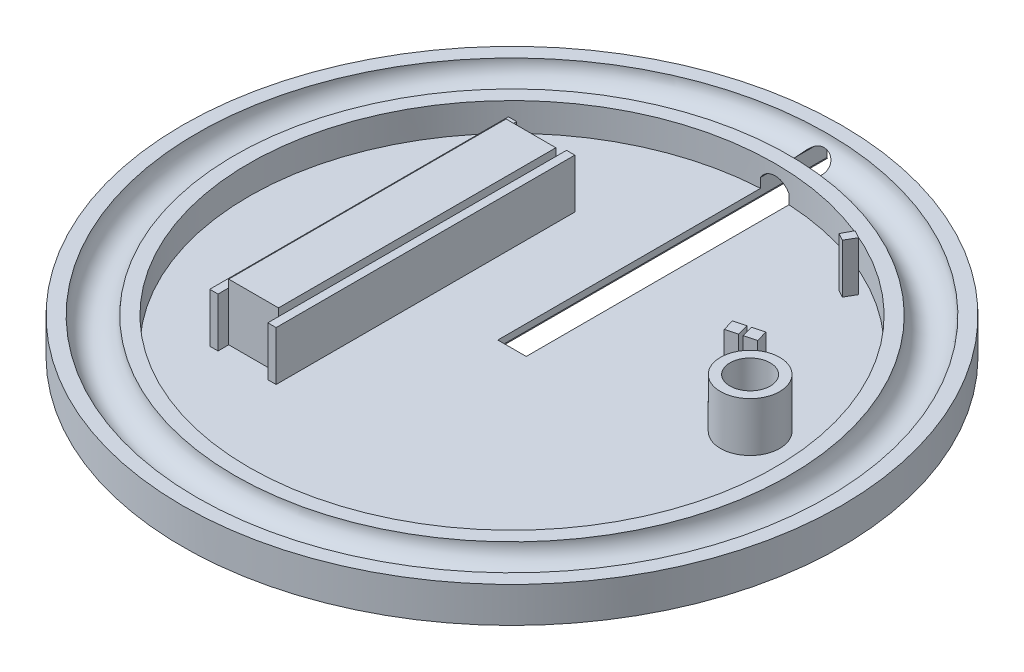
SolidWorks part; units mm, degrees
ref_plane "Front Plane" through (0, 0, 0) normal (0, 0, 1) x (1, 0, 0)
ref_plane "Top Plane" through (0, 0, 0) normal (0, 1, 0) x (1, 0, 0)
ref_plane "Right Plane" through (0, 0, 0) normal (1, 0, 0) x (0, 0, -1)
sketch "Sketch1" plane through (0, 0, 0) normal (0, 0, 1) x (1, 0, 0)
  line L0 (55, 0) -> (-55, 0) construction
  line L1 (0, 15) -> (0, 0)
  line L2 (0, 15) -> (139, 15)
  line L4 (139, 0) -> (0, 0)
  line L5 (139, 15) -> (139, 0)
  line L9 (0, 4.511) -> (0, 20.439) construction
  dimension "D1" = 139
  dimension "D4" = 15
revolve "Revolve1" add sketch "Sketch1" angle 360 about L9
sketch "Sketch2" plane through (0, 0, 0) normal (0, 0, 1) x (1, 0, 0)
  line L5 (139, 15) -> (-139, 15) construction
  line L7 (0, -8.25) -> (0, 8.25) construction
  line L8 (125, -0.0482) -> (125, 11.8) construction
  line L9 (117, 15) -> (133, 15)
  arc A0 (133, 15) -> (117, 15) centre (125, 15) cw
  point P0 (125, 15)
  dimension "D1" = 125
  dimension "D2" = 8
sketch "Sketch4" plane through (0, 15, 0) normal (0, 1, 0) x (1, 0, 0)
  line L0 (-55, 0) -> (55, 0) construction
  line L1 (-40, -58.5) -> (-61, -58.5)
  line L2 (-40, -58.5) -> (-40, 58.5)
  line L3 (-40, 58.5) -> (-61, 58.5)
  line L4 (-61, -58.5) -> (-61, 58.5)
  line L5 (-40, -58.5) -> (-61, 58.5) construction
  line L6 (-40, 58.5) -> (-61, -58.5) construction
  line L7 (0, -55) -> (0, 55) construction
  point P0 (-50.5, 0)
  dimension "D1" = 117
  dimension "D2" = 21
  dimension "D3" = 40
extrude "Boss-Extrude1" add sketch "Sketch4" along normal blind 12
sketch "Sketch5" plane through (0, 15, 0) normal (0, 1, 0) x (1, 0, 0)
  line L3 (0, 0) -> (80.5909, 19.852) construction
  line L5 (0, 0) -> (89.4848, 37.0658) construction
  line L6 (-8.25, 0) -> (8.25, 0) construction
  circle A0 centre (80.5909, 19.852) radius 12.5
  circle A1 centre (80.5909, 19.852) radius 8.5
  point P7 (0, 0)
  dimension "D1" = 25
  dimension "D2" = 22.5
  dimension "D3" = 83
  dimension "D4" = 4
extrude "Boss-Extrude2" add sketch "Sketch5" along normal blind 8.8
sketch "Sketch9" plane through (0, 15, 0) normal (0, 1, 0) x (1, 0, 0)
  line L0 (0, 0) -> (50.7046, 95.3614) construction
  line L2 (47.8861, 90.0607) -> (50.2335, 94.4754)
  line L3 (51, 88.3346) -> (53.5, 92.6647)
  line L4 (-14.85, 0) -> (14.85, 0) construction
  line L6 (0, 0) -> (54.0168, 93.5598) construction
  arc A0 (51, 88.3346) -> (47.8861, 90.0607) centre (0, 0) ccw
  arc A1 (53.5, 92.6647) -> (50.2335, 94.4754) centre (0, 0) ccw
  point P0 (0, 0)
  dimension "D2" = 102
  dimension "D3" = 107
  dimension "D1" = 60
  dimension "D5" = 2
extrude "Boss-Extrude3" add sketch "Sketch9" along normal blind 8.8
sketch "Sketch10" plane through (0, 15, 0) normal (0, 1, 0) x (1, 0, 0)
  line L0 (0, 0) -> (83.8108, 34.7156) construction
  line L1 (36.9552, 15.3073) -> (41.5746, 17.2208)
  line L2 (36.9552, 15.3073) -> (35.4244, 19.0029)
  line L3 (41.5746, 17.2208) -> (40.0438, 20.9163)
  line L4 (35.4244, 19.0029) -> (40.0438, 20.9163)
  point P0 (0, 0)
  dimension "D1" = 40
  dimension "D2" = 5
  dimension "D3" = 4
sketch "Sketch11" plane through (0, 15, 0) normal (0, 1, 0) x (1, 0, 0)
  line L0 (-50.5, 58.5) -> (-50.5, -58.5) construction
  line L1 (-40, 58.5) -> (-61, 58.5) construction
  line L2 (-61, -58.5) -> (-40, -58.5) construction
  line L3 (-14.85, 0) -> (14.85, 0) construction
  line L4 (-64.5, -63) -> (-36.5, -63)
  line L5 (-64.5, -63) -> (-64.5, 63)
  line L6 (-64.5, 63) -> (-36.5, 63)
  line L7 (-36.5, -63) -> (-36.5, 63)
  line L8 (-64.5, -63) -> (-36.5, 63) construction
  line L9 (-64.5, 63) -> (-36.5, -63) construction
  line L10 (-61, 58.5) -> (-61, -58.5)
  line L11 (-61, 58.5) -> (-61, -58.5) construction
  line L12 (-61, -58.5) -> (-40, -58.5)
  line L13 (-40, -58.5) -> (-40, 58.5)
  line L14 (-40, 58.5) -> (-61, 58.5)
  point P6 (-50.5, 0)
  dimension "D1" = 28
  dimension "D2" = 126
  dimension "D3" = 63
extrude "Boss-Extrude5" add sketch "Sketch11" along normal blind 8.8
sketch "Sketch12" plane through (0, 15, 0) normal (0, 1, 0) x (1, 0, 0)
  line L0 (80.5909, 19.852) -> (64.205, 32.3528)
  line L1 (80.5909, 19.852) -> (80.5909, 49.5381)
  line L2 (64.205, 32.3528) -> (81.5264, -30.8639) construction
  line L3 (64.205, 32.3528) -> (90.1144, 39.452) construction
  line L4 (64.9283, 32.551) -> (63.607, 37.3733)
  line L5 (64.205, 32.3528) -> (59.4962, 49.5381) construction
  line L6 (63.607, 37.3733) -> (68.4292, 38.6946)
  line L7 (68.4292, 38.6946) -> (69.7506, 33.8723)
  line L8 (69.7506, 33.8723) -> (64.9283, 32.551)
  line L9 (63.4816, 32.1546) -> (62.1603, 36.9769)
  line L10 (58.6594, 30.8333) -> (63.4816, 32.1546)
  line L11 (57.3381, 35.6556) -> (58.6594, 30.8333)
  line L12 (62.1603, 36.9769) -> (57.3381, 35.6556)
  circle A0 centre (80.5909, 19.852) radius 12.5 construction
  dimension "D1" = 20.61
  dimension "D2" = 52.66
  dimension "D3" = 5
  dimension "D4" = 5
  dimension "D5" = 0.75
sketch "Sketch13" plane through (0, 15, 0) normal (0, 1, 0) x (1, 0, 0)
  line L0 (-64.5, 63) -> (-64.5, -63) construction
  line L1 (-36.5, -63) -> (-36.5, 63) construction
  line L2 (-36.5, 63) -> (-64.5, 63) construction
  line L3 (-36.5, 63) -> (-64.5, 63)
  line L4 (-36.5, -63) -> (-36.5, 63)
  line L5 (-64.5, 63) -> (-64.5, -63)
  line L6 (-64.5, -63) -> (-36.5, -63) construction
  line L7 (-64.5, -63) -> (-36.5, -63)
  line L8 (51, 88.3346) -> (53.5, 92.6647) construction
  line L9 (50.2335, 94.4754) -> (47.8861, 90.0607) construction
  line L10 (51, 88.3346) -> (53.5, 92.6647)
  line L11 (50.2335, 94.4754) -> (47.8861, 90.0607)
  circle A0 centre (0, 0) radius 111
  circle A1 centre (0, 0) radius 139 construction
  circle A2 centre (80.5909, 19.852) radius 12.5 construction
  circle A3 centre (80.5909, 19.852) radius 12.5
  arc A4 (51, 88.3346) -> (47.8861, 90.0607) centre (0, 0) ccw construction
  arc A5 (53.5, 92.6647) -> (50.2335, 94.4754) centre (0, 0) ccw construction
  arc A6 (51, 88.3346) -> (47.8861, 90.0607) centre (0, 0) ccw
  arc A7 (53.5, 92.6647) -> (50.2335, 94.4754) centre (0, 0) ccw
  circle A8 centre (80.5909, 19.852) radius 8.5
  line M5 (53.5, 92.6647) -> (51, 88.3346)
  arc M6 (51, 88.3346) -> (47.8861, 90.0607) centre (0, 0) ccw
  line M7 (47.8861, 90.0607) -> (50.2335, 94.4754)
  arc M8 (50.2335, 94.4754) -> (53.5, 92.6647) centre (0, 0) cw
  circle M18 centre (80.5909, 19.852) radius 12.5
  line M19 (-64.5, 63) -> (-36.5, 63)
  line M20 (-36.5, 63) -> (-36.5, -63)
  line M21 (-36.5, -63) -> (-64.5, -63)
  line M22 (-64.5, -63) -> (-64.5, 63)
  dimension "D1" = 28
extrude "Cut-Extrude1" cut sketch "Sketch13" against normal offset from surface (12 mm away) 3 contours A8 | A0 M8 M5 M6 M7 M22 M19 M20 M21 M18 region at (3.9711, 15, 0.3292) region at (80.5909, 15, -19.852) up to face at (0, 0, -139)
extrude "Boss-Extrude6" add sketch "Sketch12" along normal blind 8.8 and the other way up to surface (12 mm away) contours L10 L9 L12 L11 | L7 L8 L4 L6 other way up to face at (80.5909, 3, -32.352)
sketch "Sketch14" plane through (0, 23.8, 0) normal (0, 1, 0) x (1, 0, 0)
  line L0 (-64.5, -63) -> (-36.5, -63) construction
  line L1 (-61, -58.5) -> (-40, -58.5)
  line L2 (-61, -58.5) -> (-61, -63)
  line L3 (-61, -63) -> (-40, -63)
  line L4 (-40, -58.5) -> (-40, -63)
  line L5 (-61, 58.5) -> (-40, 58.5)
  line L6 (-40, 58.5) -> (-40, 63)
  line L7 (-36.5, 63) -> (-64.5, 63) construction
  line L8 (-61, 58.5) -> (-61, 63)
  line L9 (-61, 63) -> (-40, 63)
extrude "Cut-Extrude2" cut sketch "Sketch14" against normal up to surface (20.8 mm away) up to face at (0, 3, -111)
sketch "Sketch15" plane through (0, 0, 0) normal (0, 0, 1) x (1, 0, 0)
  line L0 (139.7, 0) -> (-139.7, 0) construction
  line L1 (-6, 0) -> (6, 0)
  line L2 (-6, 0) -> (-6, 7)
  line L4 (6, 0) -> (6, 7)
  line L5 (0, -14.85) -> (0, 14.85) construction
  arc A0 (-6, 0.2572) -> (-5.8481, 0) centre (0, 3.6286) ccw
  arc A1 (5.8481, 0) -> (6, 0.2572) centre (0, 3.6286) ccw
  arc A2 (6, 7) -> (-6, 7) centre (0, 3.6286) ccw
  dimension "D1" = 7
  dimension "D2" = 12
extrude "Cut-Extrude3" cut sketch "Sketch15" along direction (0, 0, 1) on the side against the normal blind 157 contours L1 L4 A2 L2 region at (0, 4.7993, 0)
revolve "Cut-Revolve1" cut sketch "Sketch2" angle 360 about axis through (0, 23.8, 0) along (0, -1, 0)
equation "\"D3@Sketch11\"=\"D2@Sketch11\"/2"
